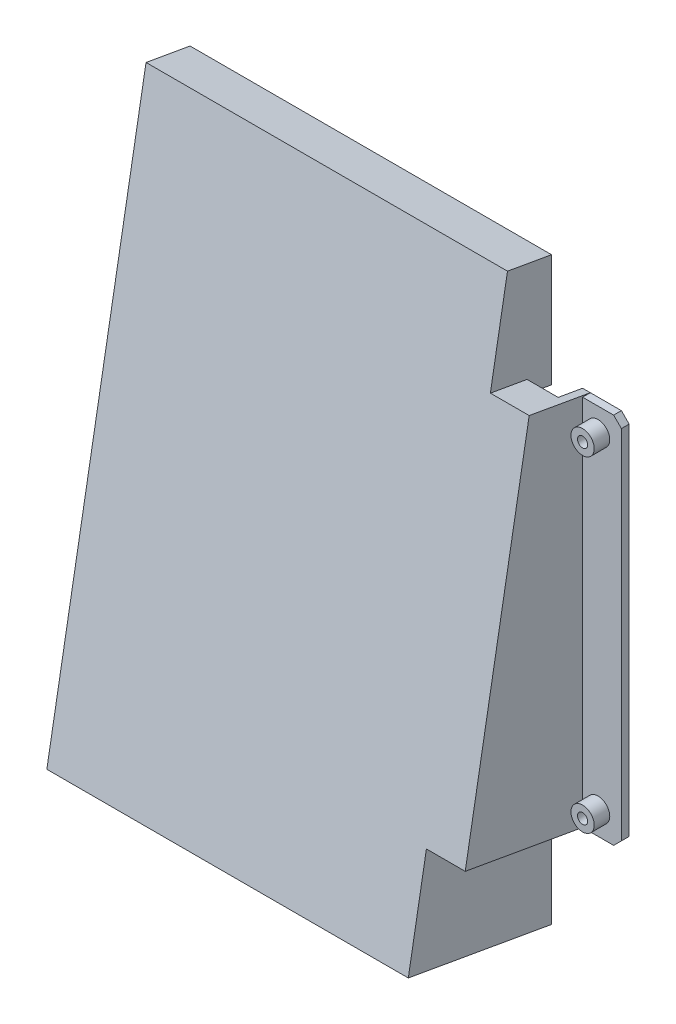
SolidWorks part; units mm, degrees
material "ABS"
ref_plane "Front Plane" through (0, 0, 0) normal (0, 0, 1) x (1, 0, 0)
ref_plane "Top Plane" through (0, 0, 0) normal (0, 1, 0) x (1, 0, 0)
ref_plane "Right Plane" through (0, 0, 0) normal (1, 0, 0) x (0, 0, -1)
sketch "Sketch1" plane through (0, 0, 0) normal (0, 0, 1) x (1, 0, 0)
  line L1 (0, 0) -> (-9.525, 0)
  line L2 (0, 0) -> (0, 76.2)
  line L3 (0, 76.2) -> (-9.525, 76.2)
  line L4 (-9.525, 0) -> (-9.525, 76.2)
  dimension "D1" = 76.2
  dimension "D2" = 9.525
extrude "Boss-Extrude1" add sketch "Sketch1" along normal blind 1.5875
chamfer "Chamfer2" distance 1.5875 angle 45 4 edges at (0, 76.2, 0.7937) (-9.525, 76.2, 0.7937) (0, 0, 0.7937) (-9.525, 0, 0.7937)
hole_wizard "#97 (0.0825) Diameter Hole1" positions "Sketch2" profile "Sketch3" hole size "#97" standard "ANSI Inch" end condition through all
sketch "Sketch2" plane through (0, 0, 1.5875) normal (0, 0, 1) x (1, 0, 0)
  line L0 (-1.5875, 76.2) -> (-7.9375, 76.2) construction
  line L1 (-7.9375, 0) -> (-1.5875, 0) construction
  line L2 (0, 4.7625) -> (-9.525, 4.7625) construction
  line L3 (0, 1.5875) -> (0, 74.6125) construction
  line L4 (-9.525, 74.6125) -> (-9.525, 1.5875) construction
  point P0 (-4.7625, 4.7625)
  point P2 (-4.7625, 71.4375)
  dimension "D1" = 4.7625
  dimension "D2" = 4.7625
sketch "Sketch3" plane through (-4.7625, 4.7625, 1.5875) normal (1, 0, 0) x (0, -1, 0)
  line L0 (0, 0) -> (0, 1.5875)
  line L1 (0, 1.5875) -> (1.0477, 1.5875)
  line L2 (1.0477, 1.5875) -> (1.0477, 0)
  line L5 (1.0477, 0) -> (0, 0)
  line L11 (0, -6.35) -> (0, 107.95) construction
  dimension "Thru Hole Dia." = 2.0955
  dimension "Thru Hole Depth" = 1.5875
ref_plane "Plane1" through (0, 38.1, 0) normal (0, 1, 0) x (1, 0, 0)
sketch "Sketch5" plane through (0, 0, 1.5875) normal (0, 0, 1) x (1, 0, 0)
  line L0 (0.8731, 38.1) -> (-0.8731, 38.1) construction
  circle A0 centre (-4.7625, 4.7625) radius 1.0478
  circle A1 centre (-4.7625, 4.7625) radius 2.3813
  circle A2 centre (-4.7625, 71.4375) radius 2.3813
  circle A3 centre (-4.7625, 71.4375) radius 1.0477
  dimension "D1" = 4.7625
  dimension "D2" = 2.0955
extrude "Boss-Extrude2" add sketch "Sketch5" along normal blind 3.175
ref_plane "Plane2" through (0, 2.2977, 13.031) normal (0, -0.1736, -0.9848) x (-1, 0, 0)
sketch "Sketch7" plane through (0, 2.2977, 13.031) normal (0, -0.1736, -0.9848) x (-1, 0, 0)
  line L1 (9.525, 75.0424) -> (7.9375, 75.0424)
  line L2 (9.525, 75.0424) -> (9.525, -0.2757)
  line L3 (9.525, -0.2757) -> (7.9375, -0.2757)
  line L4 (7.9375, 75.0424) -> (7.9375, -0.2757)
  line L8 (1.5875, 75.0424) -> (7.9375, 75.0424) construction
  line L9 (9.525, 73.479) -> (9.525, 1.5634) construction
extrude "Boss-Extrude4" add sketch "Sketch7" along normal up to surface and the other way blind 12.7 up to face at (-3.7148, 4.7625, 0)
sketch "Sketch9" plane through (-7.9375, 0, 0) normal (1, 0, 0) x (0, 0, -1)
  line L0 (0, 0) -> (-1.5875, 0)
  line L1 (-1.5875, 0) -> (0, -0.2799)
  line L2 (0, -0.2799) -> (0, 0)
extrude "Cut-Extrude1" cut sketch "Sketch9" against normal through all
sketch "Sketch10" plane through (-9.525, 0, 0) normal (-1, 0, 0) x (0, 0, 1)
  line L9 (25.5859, 4.2316) -> (12.5071, 78.4053)
  line L14 (10.4467, 75.4629) -> (22.6434, 6.2919)
  line L18 (7.841, 1.1027) -> (25.5859, 4.2316)
  line L19 (7.841, 1.1027) -> (7.4, 3.6041)
  line L20 (7.4, 3.6041) -> (22.6434, 6.2919)
  line L21 (25.5859, 4.2316) -> (1.5875, 0) construction
  line L22 (12.5071, 78.4053) -> (5.0028, 77.0821)
  line L23 (12.5071, 78.4053) -> (0, 76.2) construction
  line L24 (5.0028, 77.0821) -> (5.4439, 74.5807)
  line L25 (5.4439, 74.5807) -> (10.4467, 75.4629)
  dimension "D1" = 6.35
  dimension "D2" = 5.08
  dimension "D3" = 2.54
  dimension "D4" = 2.54
  dimension "D5" = 2.54
extrude "Boss-Extrude5" add sketch "Sketch10" along normal blind 8.89
sketch "Sketch12" plane through (-18.415, 0, 0) normal (-1, 0, 0) x (0, 0, 1)
  line L0 (25.1448, 6.733) -> (29.2898, -16.7744)
  line L1 (25.5859, 4.2316) -> (12.5071, 78.4053) construction
  line L3 (0, 2.2993) -> (0, -21.939)
  line L4 (0, -21.939) -> (29.2898, -16.7744)
  line L6 (0, 76.2) -> (0, 0) construction
  line L7 (22.6434, 6.2919) -> (7.4, 3.6041) construction
  line L8 (25.1448, 6.733) -> (0, 2.2993)
  dimension "D1" = 21.33
extrude "Boss-Extrude7" add sketch "Sketch12" against normal blind 2.54
sketch "Sketch17" plane through (-18.415, 0, 0) normal (-1, 0, 0) x (0, 0, 1)
  line L0 (12.9481, 75.9039) -> (0, 73.6208)
  line L1 (29.2898, -16.7744) -> (12.5071, 78.4053) construction
  line L2 (0, 73.6208) -> (0, 96.671)
  line L3 (0, 96.671) -> (9.0063, 98.2591)
  line L4 (9.0063, 98.2591) -> (12.9481, 75.9039)
  line L5 (0, 76.2) -> (0, 0) construction
  line L6 (5.4439, 74.5807) -> (10.4467, 75.4629) construction
  dimension "D1" = 22.7
extrude "Boss-Extrude11" add sketch "Sketch17" against normal blind 2.54
sketch "Sketch13" plane through (-18.415, 0, 0) normal (-1, 0, 0) x (0, 0, 1)
  line L0 (9.0063, 98.2591) -> (0, 96.671)
  line L3 (6.946, 95.3166) -> (26.3473, -14.714)
  line L4 (26.3473, -14.714) -> (0, -19.3598)
  line L5 (9.0063, 98.2591) -> (0, 96.671) construction
  line L6 (0, -19.3598) -> (0, -21.939)
  line L7 (0, -21.939) -> (29.2898, -16.7744)
  line L8 (29.2898, -16.7744) -> (9.0063, 98.2591)
  line L9 (0, 76.2) -> (0, 0) construction
  line L11 (6.946, 95.3166) -> (0, 94.0918)
  line L12 (0, 96.671) -> (0, 73.6208) construction
  line L13 (0, 94.0918) -> (0, 96.671)
  dimension "D1" = 2.54
  dimension "D2" = 2.54
  dimension "D3" = 2.54
extrude "Boss-Extrude8" add sketch "Sketch13" along normal blind 71.374
sketch "Sketch18" plane through (0, 4.062, 23.0366) normal (0, -0.1736, -0.9848) x (-1, 0, 0)
  line L0 (89.789, -19.0657) -> (89.789, 92.6624)
  line L1 (89.789, 92.6624) -> (87.249, 92.6624)
  line L2 (87.249, 92.6624) -> (87.249, -19.0657)
  line L3 (89.789, -19.0657) -> (18.415, -19.0657) construction
  line L4 (87.249, -19.0657) -> (89.789, -19.0657)
  dimension "D1" = 2.54
extrude "Boss-Extrude12" add sketch "Sketch18" along normal up to surface (7.0531 mm away) up to face at (-41.3597, -12.9998, 0)
sketch "Sketch19" plane through (0, -21.2774, 3.7518) normal (0, -0.9848, 0.1736) x (-1, 0, 0)
  line L0 (15.875, 3.8097) -> (15.875, -25.932) construction
  line L1 (28.575, -5.612) -> (77.089, -5.612)
  line L2 (28.575, -5.612) -> (28.575, -18.312)
  line L3 (28.575, -18.312) -> (77.089, -18.312)
  line L4 (77.089, -5.612) -> (77.089, -18.312)
  line L5 (89.789, 3.8097) -> (89.789, -25.932) construction
  line L6 (15.875, -25.932) -> (89.789, -25.932) construction
  dimension "D1" = 12.7
  dimension "D2" = 12.7
  dimension "D3" = 12.7
  dimension "D4" = 7.62
extrude "Cut-Extrude2" cut sketch "Sketch19" against normal up to surface (2.54 mm away) and the other way through all up to face at (-52.832, -17.0369, 13.1737)
equation "\"D4@Sketch10\"=\"D3@Sketch10\""
equation "\"D5@Sketch10\"=\"D3@Sketch10\""
